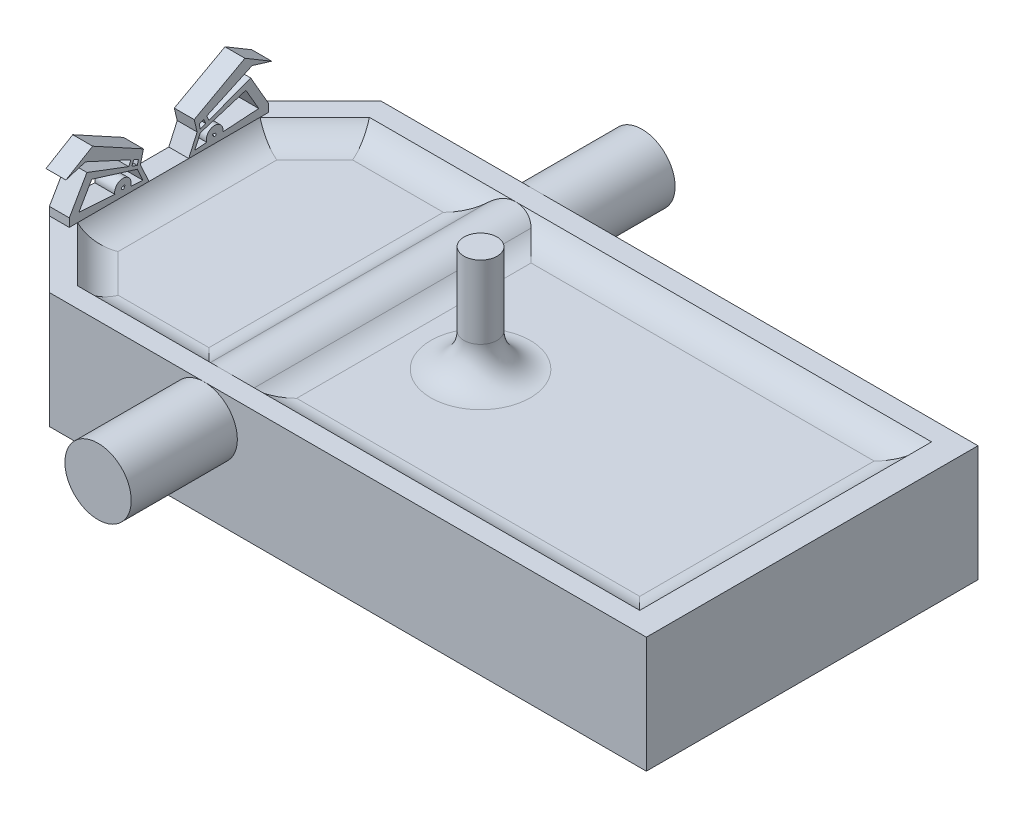
SolidWorks part; units mm, degrees
ref_plane "Alzado" through (0, 0, 0) normal (0, 0, 1) x (1, 0, 0)
ref_plane "Planta" through (0, 0, 0) normal (0, 1, 0) x (1, 0, 0)
ref_plane "Vista lateral" through (0, 0, 0) normal (1, 0, 0) x (0, 0, -1)
sketch "Croquis1" plane through (0, 0, 0) normal (0, 1, 0) x (1, 0, 0)
  line L0 (-50, 15) -> (-40, 25)
  line L1 (-40, 25) -> (50, 25)
  line L2 (-50, 15) -> (-50, -15)
  line L3 (-40, -25) -> (50, -25)
  line L4 (50, 25) -> (50, -25)
  line L5 (0, -25) -> (0, 25) construction
  line L7 (0, 0) -> (-14.8902, 0) construction
  line L8 (-50, -15) -> (-40, -25)
  point P0 (0, 0)
  point P13 (0, 0)
  dimension "D1" = 100
  dimension "D2" = 50
  dimension "D3" = 50
extrude "Saliente-Extruir1" add sketch "Croquis1" along normal blind 5
sketch "Croquis2" plane through (0, 0, 0) normal (0, 0, 1) x (1, 0, 0)
  line L0 (0, 0) -> (0, 2.5) construction
  line L1 (0, 2.5) -> (-16.6667, 2.5) construction
  line L2 (-16.6667, 2.5) -> (-33.3333, 2.5) construction
  line L3 (-33.3333, 2.5) -> (-50, 2.5) construction
  line L4 (-50, 5) -> (-50, 0) construction
  circle A0 centre (-16.6667, 2.5) radius 5
  dimension "D2" = 10
  dimension "D1" = 2.5
extrude "Saliente-Extruir2" add sketch "Croquis2" along normal mid plane 82
sketch "Croquis3" plane through (0, 5, 0) normal (0, 1, 0) x (1, 0, 0)
  circle A0 centre (0, 0) radius 2.5
  dimension "D1" = 5
extrude "Saliente-Extruir3" add sketch "Croquis3" along normal blind 16
sketch "Croquis24" plane through (0, 0, 0) normal (0, -1, 0) x (1, 0, 0)
  line L0 (46, 22) -> (-38.7574, 22)
  line L1 (-38.7574, 22) -> (-47, 13.7574)
  line L2 (-47, 13.7574) -> (-47, -13.7574)
  line L3 (-47, -13.7574) -> (-38.7574, -22)
  line L4 (-38.7574, -22) -> (46, -22)
  line L5 (46, -22) -> (46, 22)
  line L6 (-50, 15) -> (-40, 25) construction
  line L7 (-40, 25) -> (-20.9968, 25) construction
  line L8 (50, 25) -> (50, -25) construction
  line L9 (50, -25) -> (-12.3365, -25) construction
  line L11 (-50, -15) -> (-50, 15) construction
  line L12 (-40, -25) -> (-50, -15) construction
  line L13 (50, 25) -> (-40, 25)
  line L14 (-40, 25) -> (-50, 15)
  line L15 (-50, 15) -> (-50, -15)
  line L16 (-50, -15) -> (-40, -25)
  line L17 (-40, -25) -> (50, -25)
  line L18 (50, -25) -> (50, 25)
  dimension "D1" = 3
  dimension "D2" = 4
  dimension "D3" = 3
  dimension "D4" = 3
  dimension "D5" = 3
  dimension "D6" = 3
extrude "Saliente-Extruir10" add sketch "Croquis24" along normal blind 10 and the other way blind 7.5
fillet "Redondeo3" radius 5 11 edges at (16.8317, 5, -22) (46, 5, 0) (-20.9968, 5, 0) (-12.3365, 5, 0) (-29.8771, 5, 22) (-42.8787, 5, 17.8787) (-47, 5, 0) (-42.8787, 5, -17.8787) (-29.8771, 5, -22) (16.8317, 5, 22) (0, 5, 2.5)
sketch "Croquis25" plane through (-50, 0, 0) normal (-1, 0, 0) x (0, 0, 1)
  line L0 (0, 0) -> (0, 7.5) construction
  line L1 (15, 7.5) -> (-15, 7.5) construction
  line L2 (-3, 7.5) -> (3, 7.5) construction
  line L3 (-3, 7.5) -> (-4.272, 10.3215)
  line L4 (-6.0477, 10.9662) -> (-12.3444, 13.3497)
  line L5 (-12.3444, 13.3497) -> (-15, 8.75)
  line L6 (-15, 8.75) -> (-15, 7.5)
  line L7 (-15, 7.5) -> (-3, 7.5)
  line L8 (-4.272, 10.3215) -> (-3.8258, 12.1715)
  line L9 (-3.8258, 12.1715) -> (-11.4787, 16.3497)
  line L10 (-11.4787, 16.3497) -> (-15.5141, 13.9493)
  line L11 (-15.5141, 13.9493) -> (-12.5661, 14.8497)
  line L12 (-12.5661, 14.8497) -> (-5.713, 11.6928)
  line L13 (-5.713, 11.6928) -> (-6.0477, 10.9662)
  line L14 (-5.2589, 11.4836) -> (-4.5813, 11.1715)
  line L16 (-4.7493, 10.4747) -> (-5.579, 10.7887)
  line L17 (-5.579, 10.7887) -> (-5.2589, 11.4836)
  line L18 (-4.5813, 11.1715) -> (-4.7493, 10.4747)
  line L19 (-13.5566, 8.75) -> (-11.6227, 12.0997)
  line L20 (-11.6227, 12.0997) -> (-4.7493, 9.9747)
  line L21 (-4.7493, 9.9747) -> (-3.9155, 8.125)
  line L22 (-3.9155, 8.125) -> (-5.7238, 8.2422)
  line L23 (-3.9155, 8.125) -> (-5.7238, 8.2422) construction
  line L24 (-6.9155, 8.3195) -> (-6.9155, 8.6195) construction
  line L25 (-8.1459, 8.3992) -> (-13.5566, 8.75)
  line L26 (0, 7.5) -> (0, 12.6588) construction
  line L27 (5.2589, 11.4836) -> (4.5813, 11.1715)
  line L28 (5.579, 10.7887) -> (5.2589, 11.4836)
  line L29 (4.7493, 10.4747) -> (5.579, 10.7887)
  line L30 (4.5813, 11.1715) -> (4.7493, 10.4747)
  line L31 (15, 7.5) -> (3, 7.5)
  line L32 (15, 8.75) -> (15, 7.5)
  line L33 (12.3444, 13.3497) -> (15, 8.75)
  line L34 (6.0477, 10.9662) -> (12.3444, 13.3497)
  line L35 (5.713, 11.6928) -> (6.0477, 10.9662)
  line L36 (12.5661, 14.8497) -> (5.713, 11.6928)
  line L37 (15.5141, 13.9493) -> (12.5661, 14.8497)
  line L38 (11.4787, 16.3497) -> (15.5141, 13.9493)
  line L39 (3.8258, 12.1715) -> (11.4787, 16.3497)
  line L40 (4.272, 10.3215) -> (3.8258, 12.1715)
  line L41 (3, 7.5) -> (4.272, 10.3215)
  line L42 (3.9155, 8.125) -> (5.7238, 8.2422)
  line L43 (4.7493, 9.9747) -> (3.9155, 8.125)
  line L44 (11.6227, 12.0997) -> (4.7493, 9.9747)
  line L45 (13.5566, 8.75) -> (11.6227, 12.0997)
  line L46 (8.1459, 8.3992) -> (13.5566, 8.75)
  arc A0 (-5.7238, 8.2422) -> (-8.1459, 8.3992) centre (-6.9155, 8.6195) ccw
  arc A1 (-6.8557, 8.823) -> (-6.7244, 8.7116) centre (-6.9155, 8.6195) ccw
  arc A2 (6.8557, 8.823) -> (6.7244, 8.7116) centre (6.9155, 8.6195) cw
  arc A3 (5.7238, 8.2422) -> (8.1459, 8.3992) centre (6.9155, 8.6195) cw
  spline S0 degree 3 poles (-6.7244, 8.7116) (-6.6768, 8.7223) (-6.5566, 8.6819) (-6.5777, 8.8983) (-6.7538, 8.8726) (-6.8355, 8.8377) (-6.8557, 8.823) knots 0 0 0 0 0.159221 0.274522 0.503394 0.587778 0.587778 0.587778 0.587778
  spline S1 degree 3 poles (6.7244, 8.7116) (6.6768, 8.7223) (6.5566, 8.6819) (6.5777, 8.8983) (6.7538, 8.8726) (6.8355, 8.8377) (6.8557, 8.823) knots 0 0 0 0 0.159221 0.274522 0.503394 0.587778 0.587778 0.587778 0.587778
  point P8 (0, 7.5)
  point P33 (-15, 8.125)
  dimension "D14" = 2.5
  dimension "D1" = 3
  dimension "D2" = 150
  dimension "D3" = 135
  dimension "D4" = 1.5
  dimension "D6" = 0.8
  dimension "D7" = 0.5
  dimension "D8" = 0.5
  dimension "D9" = 1.25
  dimension "D10" = 1.25
  dimension "D11" = 0.5
  dimension "D12" = 3
  dimension "D13" = 0.3
  dimension "D15" = 4
  dimension "D16" = 1.25
  dimension "D17" = 1.85
  dimension "D18" = 1
  dimension "D19" = 1.5
extrude "Saliente-Extruir11" add sketch "Croquis25" against normal up to vertex (3 mm away) up to point (-47, 7.5, 13.7574)
sketch "Croquis26" plane through (-50, 0, 0) normal (-1, 0, 0) x (0, 0, 1)
  line L0 (0, 0) -> (0, -2) construction
  line L1 (-6.4571, -2) -> (6.4571, -2)
  line L2 (6.4571, -2) -> (8.2123, -0.1)
  line L3 (8.2123, -0.1) -> (5.9571, -0.6)
  line L4 (5.9571, -0.6) -> (-5.9571, -0.6)
  line L5 (-5.9571, -0.6) -> (-8.2123, -0.1)
  line L6 (-8.2123, -0.1) -> (-6.4571, -2)
  line L7 (-0.875, 3.5155) -> (0.875, 3.5155)
  line L8 (0.875, 3.5155) -> (0, 2)
  line L9 (0, 2) -> (-0.875, 3.5155)
  point P6 (0, -2)
  point P12 (0, 0)
  point P14 (0, 3.5155)
  dimension "D1" = 2
  dimension "D2" = 0.5
  dimension "D3" = 0.5
  dimension "D4" = 0.5
  dimension "D5" = 1.4
  dimension "D6" = 2
  dimension "D7" = 1.75
extrude "Cortar-Extruir1" cut sketch "Croquis26" against normal up to surface (3 mm away) up to face at (-47, -5, 0)
